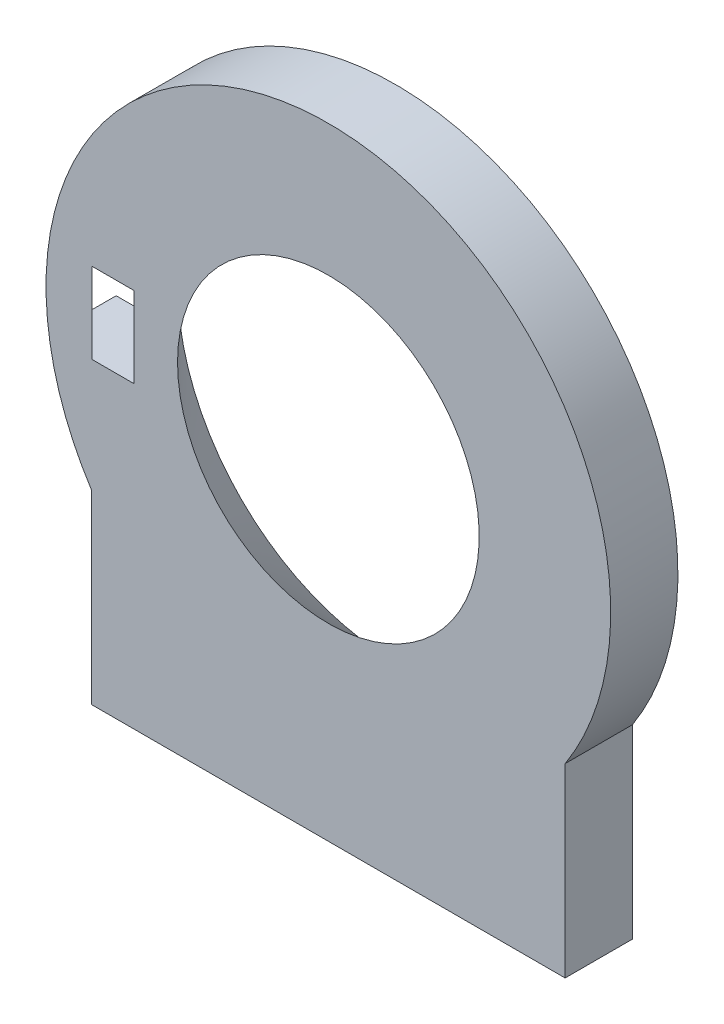
SolidWorks part; units mm, degrees
ref_plane "Front Plane" through (0, 0, 0) normal (0, 0, 1) x (1, 0, 0)
ref_plane "Top Plane" through (0, 0, 0) normal (0, 1, 0) x (1, 0, 0)
ref_plane "Right Plane" through (0, 0, 0) normal (1, 0, 0) x (0, 0, -1)
sketch "Sketch1" plane through (0, 0, 0) normal (0, 0, 1) x (1, 0, 0)
  line L0 (-35.221, -22.8798) -> (-35.221, -50.5)
  line L1 (-35.221, -50.5) -> (35.221, -50.5)
  line L2 (35.221, -50.5) -> (35.221, -22.8798)
  line L3 (5.5, 0) -> (-5.5, 0) construction
  arc A0 (-35.221, -22.8798) -> (35.221, -22.8798) centre (0, 0) cw
  dimension "D1" = 42
  dimension "D2" = 50.5
extrude "Boss-Extrude1" add sketch "Sketch1" along normal blind 10 contours A0 L2 L1 L0
sketch "Sketch2" plane through (0, 0, 0) normal (0, 0, -1) x (-1, 0, 0)
  line L0 (5.5, 0) -> (-5.5, 0) construction
  line L1 (32.6389, 6) -> (49.7918, 6)
  line L2 (32.6389, 6) -> (32.6389, -6)
  line L3 (32.6389, -6) -> (49.7918, -6)
  line L4 (49.7918, 6) -> (49.7918, -6)
  dimension "D1" = 12
  dimension "D2" = 6
sketch "Sketch3" plane through (0, 0, 10) normal (0, 0, 1) x (1, 0, 0)
  line L0 (5.5, 0) -> (-5.5, 0) construction
  line L1 (-35.1643, 6) -> (-28.9053, 6)
  line L2 (-35.1643, 6) -> (-35.1643, -6)
  line L3 (-35.1643, -6) -> (-28.9053, -6)
  line L4 (-28.9053, 6) -> (-28.9053, -6)
  dimension "D1" = 12
  dimension "D2" = 6
loft "Cut-Loft1" cut profiles "Sketch3", "Sketch2" connector at (-28.9053, 6, 10) connector at (-32.6389, 6, 0)
sketch "Sketch4" plane through (0, 0, 0) normal (0, 0, -1) x (-1, 0, 0)
  circle A0 centre (0, 0) radius 22.4376
extrude "Cut-Extrude1" cut sketch "Sketch4" against normal blind 30
chamfer "Chamfer1" distance 10 angle 45 1 edges at (-22.4376, 0, 0)
